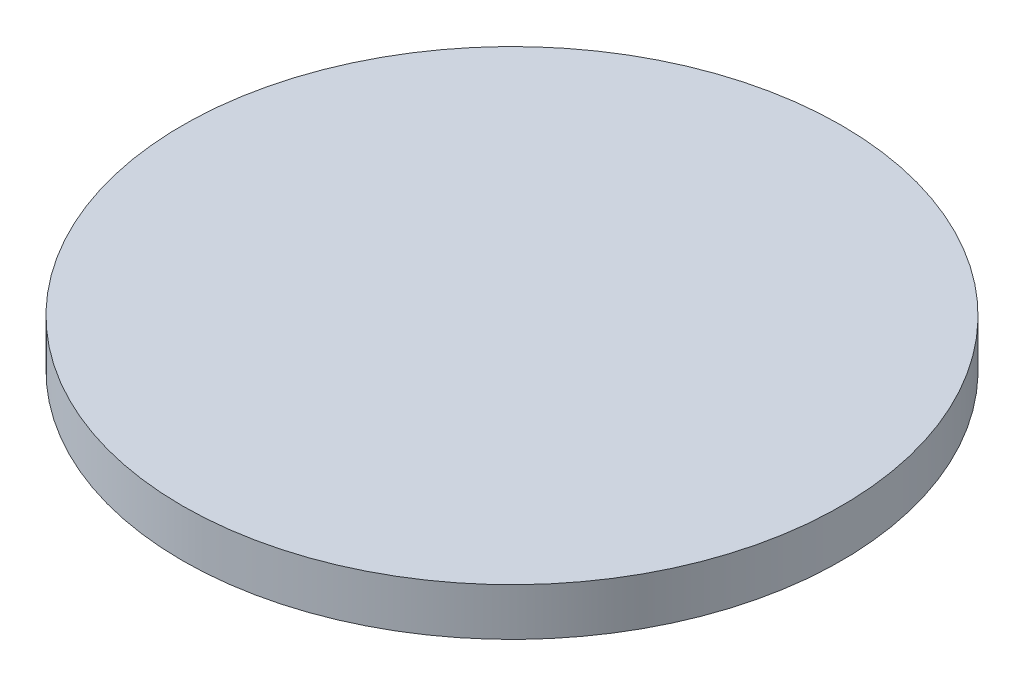
SolidWorks part; units mm, degrees
ref_plane "Front Plane" through (0, 0, 0) normal (0, 0, 1) x (1, 0, 0)
ref_plane "Top Plane" through (0, 0, 0) normal (0, 1, 0) x (1, 0, 0)
ref_plane "Right Plane" through (0, 0, 0) normal (1, 0, 0) x (0, 0, -1)
sketch "Sketch1" plane through (0, 0, 0) normal (0, 0, 1) x (1, 0, 0)
  line L0 (0, 97.3499) -> (0, 64.4918) construction
  arc A0 (119.5774, -82.2021) -> (144.837, 8.843) centre (0, 0) ccw
  point P0 (144.837, 8.843)
  point P1 (123.7156, -75.8313)
  point P2 (119.5774, -82.2021)
  point P3 (144.9679, -6.345)
  point P6 (135.9119, -50.832)
  dimension "D1" = 11
  dimension "D2" = 18
sketch3d "3DSketch1"
  circle A0 centre (0, 97.3499, 0) radius 5.9059
  point P3 (0, 103.2558, 0)
extrude "Boss-Extrude1" add sketch "3DSketch1" along direction (0, -1, 0) on the side against the normal blind 0.85
